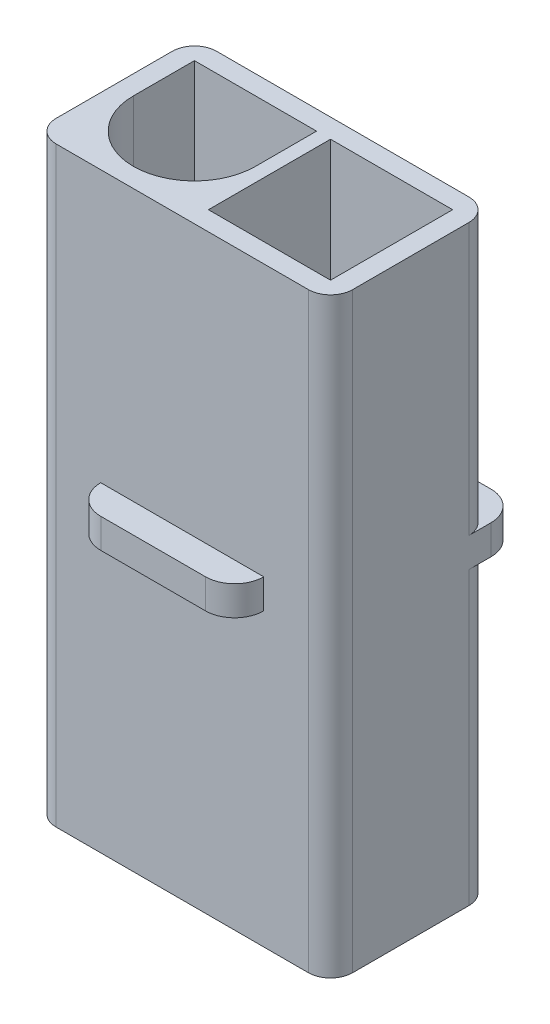
SolidWorks part; units mm, degrees
ref_plane "Front Plane" through (0, 0, 0) normal (0, 0, 1) x (1, 0, 0)
ref_plane "Top Plane" through (0, 0, 0) normal (0, 1, 0) x (1, 0, 0)
ref_plane "Right Plane" through (0, 0, 0) normal (1, 0, 0) x (0, 0, -1)
sketch "Sketch1" plane through (0, 0, 0) normal (0, 1, 0) x (1, 0, 0)
  line L1 (-6.68, -3.615) -> (6.68, -3.615)
  line L2 (-6.68, -3.615) -> (-6.68, 3.615)
  line L3 (-6.68, 3.615) -> (6.68, 3.615)
  line L4 (6.68, -3.615) -> (6.68, 3.615)
  line L5 (-6.68, -3.615) -> (6.68, 3.615) construction
  line L6 (-6.68, 3.615) -> (6.68, -3.615) construction
  point P0 (0, 0)
  dimension "D1" = 7.23
  dimension "D2" = 13.36
extrude "Boss-Extrude1" add sketch "Sketch1" along normal mid plane 26.65
sketch "Sketch2" plane through (0, 13.325, 0) normal (0, 1, 0) x (1, 0, 0)
  line L0 (-5.815, 2.75) -> (-0.315, 2.75)
  line L1 (-0.315, 2.75) -> (-0.315, 0)
  line L2 (-5.815, 0) -> (-5.815, 2.75)
  line L3 (5.815, 0) -> (6.68, 0) construction
  line L4 (0.315, 2.75) -> (5.815, 2.75)
  line L5 (0.315, 2.75) -> (0.315, -2.75)
  line L6 (0.315, -2.75) -> (5.815, -2.75)
  line L7 (5.815, 2.75) -> (5.815, -2.75)
  line L8 (6.68, -3.615) -> (6.68, 3.615) construction
  line L9 (5.815, 2.75) -> (5.815, 3.615) construction
  line L10 (6.68, 3.615) -> (-6.68, 3.615) construction
  line L11 (-5.815, 2.75) -> (-6.68, 2.75) construction
  line L12 (-6.68, 3.615) -> (-6.68, -3.615) construction
  arc A0 (-0.315, 0) -> (-5.815, 0) centre (-3.065, 0) cw
  dimension "D1" = 5.5
  dimension "D2" = 0.865
extrude "Cut-Extrude1" cut sketch "Sketch2" against normal blind 10
sketch "Sketch3" plane through (0, -13.325, 0) normal (0, -1, 0) x (1, 0, 0)
  line L0 (-3.065, 0) -> (3.065, 0) construction
  circle A1 centre (-3.065, 0) radius 2.75
  arc A2 (-0.315, 0) -> (-5.815, 0) centre (-3.065, 0) ccw construction
  circle A3 centre (3.065, 0) radius 2.75
  dimension "D1" = 5.5
extrude "Cut-Extrude2" cut sketch "Sketch3" against normal blind 11.75
sketch "Sketch4" plane through (0, 0, 0) normal (1, 0, 0) x (0, 0, -1)
  line L0 (3.615, 13.325) -> (5.145, 10.975)
  line L1 (5.145, 10.975) -> (3.615, 10.975)
  line L2 (3.615, 13.325) -> (3.615, -13.325) construction
  line L3 (3.615, 10.975) -> (3.615, 13.325)
  line L4 (-3.615, 13.325) -> (-3.615, -13.325) construction
  dimension "D1" = 2.35
  dimension "D2" = 8.76
extrude "Boss-Extrude2" add sketch "Sketch4" along normal mid plane 3.6
ref_plane "Plane1" through (0, -0.215, 0) normal (0, 1, 0) x (1, 0, 0)
sketch "Sketch5" plane through (0, -0.215, 0) normal (0, 1, 0) x (1, 0, 0)
  line L0 (-5.37, 4.925) -> (-4.56, 4.925)
  line L1 (4.56, 4.925) -> (5.37, 4.925)
  line L2 (-2.36, -4.925) -> (2.36, -4.925)
  line L3 (-1.8, 3.615) -> (-6.68, 3.615) construction
  line L4 (6.68, 3.615) -> (1.8, 3.615) construction
  line L5 (-6.68, -3.615) -> (6.68, -3.615) construction
  line L6 (-6.68, 3.615) -> (-3.25, 3.615)
  line L7 (3.25, 3.615) -> (6.68, 3.615)
  line L8 (3.67, -3.615) -> (-3.67, -3.615)
  line L9 (-5.37, 4.925) -> (-5.37, 3.615) construction
  line L10 (-2.36, -3.615) -> (-2.36, -4.925) construction
  line L11 (-6.68, 3.615) -> (-6.68, -3.615) construction
  line L12 (6.68, -3.615) -> (6.68, 3.615) construction
  arc A0 (-4.56, 4.925) -> (-3.25, 3.615) centre (-4.56, 3.615) cw
  arc A1 (-5.37, 4.925) -> (-6.68, 3.615) centre (-5.37, 3.615) ccw
  arc A2 (4.56, 4.925) -> (3.25, 3.615) centre (4.56, 3.615) ccw
  arc A3 (5.37, 4.925) -> (6.68, 3.615) centre (5.37, 3.615) cw
  arc A4 (2.36, -4.925) -> (3.67, -3.615) centre (2.36, -3.615) ccw
  arc A5 (-2.36, -4.925) -> (-3.67, -3.615) centre (-2.36, -3.615) cw
  point P24 (0, -3.615)
  dimension "D1" = 3.43
  dimension "D2" = 1.31
  dimension "D3" = 7.34
extrude "Boss-Extrude3" add sketch "Sketch5" along normal blind 1.33
fillet "Fillet1" radius 1 6 edges at (6.68, 7.22, -3.615) (-6.68, 7.22, -3.615) (6.68, 0, 3.615) (-6.68, 0, 3.615) (6.68, -6.77, -3.615) (-6.68, -6.77, -3.615)
